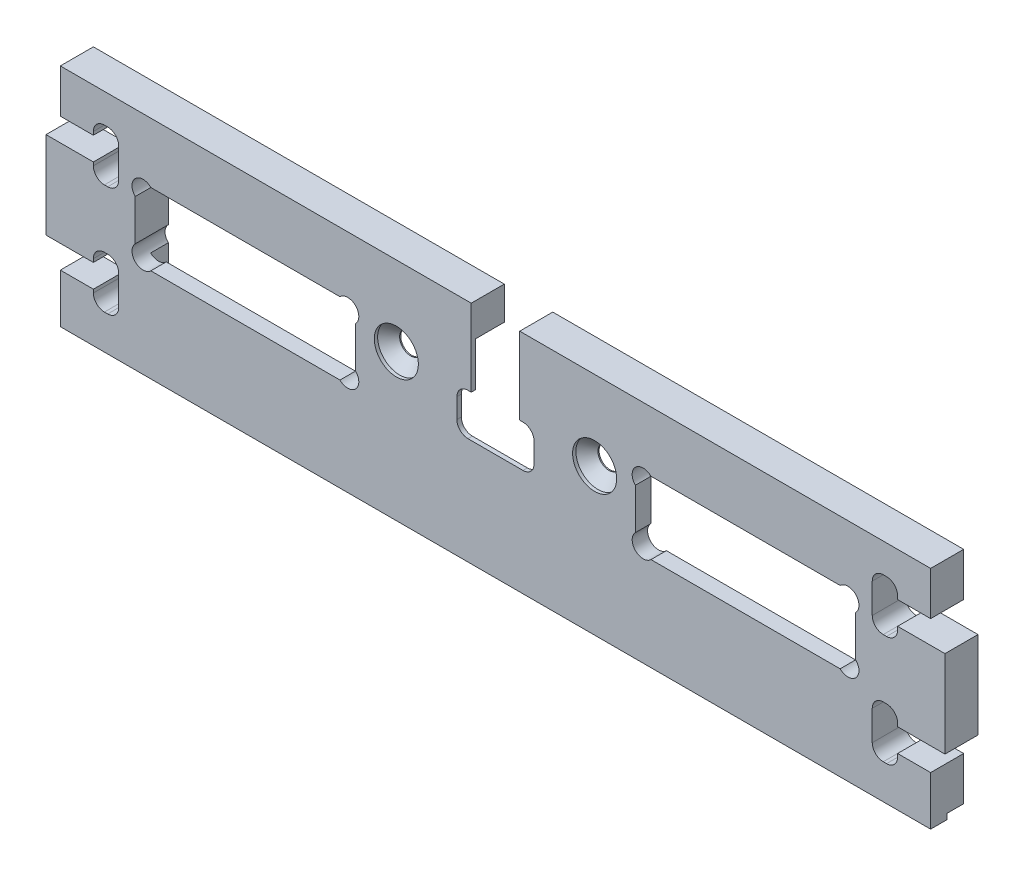
SolidWorks part; units mm, degrees
ref_plane "Front Plane" through (0, 0, 0) normal (0, 0, 1) x (1, 0, 0)
ref_plane "Top Plane" through (0, 0, 0) normal (0, 1, 0) x (1, 0, 0)
ref_plane "Right Plane" through (0, 0, 0) normal (1, 0, 0) x (0, 0, -1)
sketch "Sketch1" plane through (0, 0, 0) normal (0, 0, 1) x (1, 0, 0)
  line L0 (-39.5, 0) -> (39.5, 0) construction
  line L1 (-39.5, 10) -> (39.5, 10)
  line L2 (-39.5, 10) -> (-39.5, -10)
  line L3 (-39.5, -10) -> (39.5, -10)
  line L4 (39.5, 10) -> (39.5, -10)
  line L5 (-39.5, 10) -> (39.5, -10) construction
  line L6 (-39.5, -10) -> (39.5, 10) construction
  line L7 (0, 10) -> (0, -10) construction
  line L9 (-40.8, -3.95) -> (-39.5, -3.95)
  line L10 (-40.8, -3.95) -> (-40.8, 3.95)
  line L11 (-40.8, 3.95) -> (-39.5, 3.95)
  line L12 (-39.5, -3.95) -> (-39.5, 3.95)
  line L13 (-40.8, -3.95) -> (-39.5, 3.95) construction
  line L14 (-40.8, 3.95) -> (-39.5, -3.95) construction
  line L16 (40.8, 3.95) -> (39.5, 3.95)
  line L17 (40.8, -3.95) -> (40.8, 3.95)
  line L18 (40.8, -3.95) -> (39.5, -3.95)
  line L19 (-39.5, 5) -> (39.5, 5) construction
  line L20 (-35.35, 7.35) -> (-35.35, 2.65) construction
  line L21 (-36.5, 3.95) -> (-39.5, 3.95)
  line L22 (-36.5, 3.95) -> (-36.5, 6.05)
  line L23 (-36.5, 6.05) -> (-39.5, 6.05)
  line L24 (-39.5, 3.95) -> (-39.5, 6.05)
  line L25 (-36.5, 3.95) -> (-39.5, 6.05) construction
  line L26 (-36.5, 6.05) -> (-39.5, 3.95) construction
  line L27 (-34.2, 7.35) -> (-36.5, 7.35)
  line L28 (-34.2, 7.35) -> (-34.2, 2.65)
  line L29 (-34.2, 2.65) -> (-36.5, 2.65)
  line L30 (-36.5, 7.35) -> (-36.5, 2.65)
  line L31 (-34.2, 7.35) -> (-36.5, 2.65) construction
  line L32 (-34.2, 2.65) -> (-36.5, 7.35) construction
  line L33 (-34.2, -7.35) -> (-36.5, -7.35)
  line L34 (-34.2, -7.35) -> (-34.2, -2.65)
  line L35 (-34.2, -2.65) -> (-36.5, -2.65)
  line L36 (-36.5, -7.35) -> (-36.5, -2.65)
  line L37 (-36.5, -3.95) -> (-39.5, -3.95)
  line L38 (-36.5, -6.05) -> (-39.5, -6.05)
  line L39 (36.5, 3.95) -> (39.5, 3.95)
  line L40 (36.5, 6.05) -> (39.5, 6.05)
  line L41 (36.5, 7.35) -> (36.5, 2.65)
  line L42 (34.2, 7.35) -> (36.5, 7.35)
  line L43 (34.2, 7.35) -> (34.2, 2.65)
  line L44 (34.2, 2.65) -> (36.5, 2.65)
  line L45 (34.2, -2.65) -> (36.5, -2.65)
  line L46 (34.2, -7.35) -> (34.2, -2.65)
  line L47 (34.2, -7.35) -> (36.5, -7.35)
  line L48 (36.5, -7.35) -> (36.5, -2.65)
  line L49 (36.5, -6.05) -> (39.5, -6.05)
  line L50 (36.5, -3.95) -> (39.5, -3.95)
  point P0 (0, 0)
  point P10 (-40.15, 0)
  point P15 (-38, 5)
  point P35 (-35.35, 5)
  dimension "D1" = 79
  dimension "D2" = 20
  dimension "D4" = 1.3
  dimension "D7" = 5
  dimension "D8" = 2.1
  dimension "D9" = 3
  dimension "D10" = 2.3
  dimension "D11" = 4.7
extrude "Base shape" add sketch "Sketch1" along normal blind 3 contours L4 L1 L2 L3 | L9 L2 L11 L10 | L16 L4 L18 L17 region at (0, 0, 0) region at (-40.15, 0, 0) region at (40.15, 0, 0)
sketch "Sketch4" plane through (0, -10, 0) normal (0, -1, 0) x (1, 0, 0)
  line L0 (39.5, 3) -> (39.5, 0) construction
  line L1 (-39.5, 3) -> (39.5, 3)
  line L2 (-39.5, 3) -> (-39.5, 1.5)
  line L3 (-39.5, 1.5) -> (39.5, 1.5)
  line L4 (39.5, 3) -> (39.5, 1.5)
extrude "Floor lip" add sketch "Sketch4" along normal blind 0.5
sketch "Sketch6" plane through (0, 0, 0) normal (0, 0, -1) x (-1, 0, 0)
  line L0 (0, 0) -> (0, -10) construction
  line L1 (39.5, -10) -> (-39.5, -10) construction
  line L2 (-4, -10) -> (4, -10) construction
  line L3 (39.5, -10) -> (-39.5, -10) construction
  line L4 (-4, -9) -> (4, -9)
  line L5 (-4, -11) -> (4, -11)
  arc A0 (-4, -9) -> (-4, -11) centre (-4, -10) ccw
  arc A1 (4, -11) -> (4, -9) centre (4, -10) ccw
  point P9 (0, -10)
  dimension "D1" = 2
  dimension "D2" = 8
extrude "Nail cutout" cut sketch "Sketch6" against normal up to surface (1.5 mm away) up to face at (0, -10.25, 1.5)
sketch "Sketch3" plane through (-40.8, 0, 0) normal (-1, 0, 0) x (0, 0, 1)
  line L0 (0, 6.05) -> (3, 3.95) construction
  line L1 (0, 6.05) -> (3, 6.05)
  line L2 (0, 6.05) -> (0, 3.95)
  line L3 (0, 3.95) -> (3, 3.95)
  line L4 (3, 6.05) -> (3, 3.95)
  line L5 (0, -3.95) -> (3, -6.05) construction
  line L6 (0, -3.95) -> (3, -3.95)
  line L7 (0, -3.95) -> (0, -6.05)
  line L8 (0, -6.05) -> (3, -6.05)
  line L9 (3, -3.95) -> (3, -6.05)
  point P6 (1.5, 5)
  point P13 (1.5, -5)
ref_axis "Tap axis top" through (-53.7846, 5, 1.5) along (1, 0, 0)
ref_axis "Tap axis bottom" through (-54.2844, -5, 1.5) along (1, 0, 0)
fillet "Mill fillets" radius 1 16 edges at (36.5, -7.35, 1.5) (36.5, 2.65, 1.5) (34.2, 2.65, 1.5) (34.2, -7.35, 1.5) (36.5, -2.65, 1.5) (36.5, 7.35, 1.5) (34.2, -2.65, 1.5) (34.2, 7.35, 1.5) (-36.5, -2.65, 1.5) (-34.2, -2.65, 1.5) (-34.2, -7.35, 1.5) (-36.5, -7.35, 1.5) (-36.5, 2.65, 1.5) (-34.2, 2.65, 1.5) (-34.2, 7.35, 1.5) (-36.5, 7.35, 1.5)
sketch "Sketch8" [suppressed] plane through (0, 0, 3) normal (0, 0, 1) x (1, 0, 0)
  line L0 (-40.8, 0) -> (40.8, 0) construction
  line L1 (-40.8, -3.95) -> (-40.8, 3.95) construction
  line L2 (40.8, -3.95) -> (40.8, 3.95) construction
  line L4 (-24.5, 5.15) -> (24.5, 5.15)
  line L5 (-25.5, 4.15) -> (-25.5, -4.15)
  line L6 (-24.5, -5.15) -> (24.5, -5.15)
  line L7 (25.5, 4.15) -> (25.5, -4.15)
  line L8 (-25.5, 5.15) -> (25.5, -5.15) construction
  line L9 (-25.5, -5.15) -> (25.5, 5.15) construction
  arc A0 (24.5, -5.15) -> (25.5, -4.15) centre (24.5, -4.15) ccw
  arc A1 (24.5, 5.15) -> (25.5, 4.15) centre (24.5, 4.15) cw
  arc A2 (-25.5, -4.15) -> (-24.5, -5.15) centre (-24.5, -4.15) ccw
  arc A3 (-24.5, 5.15) -> (-25.5, 4.15) centre (-24.5, 4.15) ccw
  point P6 (0, 0)
  dimension "D3" = 1
  dimension "D1" = 51
  dimension "D2" = 10.3
extrude "Led strip pocket" [suppressed] cut sketch "Sketch8" against normal offset from surface (2.5 mm away) 0.5 up to face at (0, -0.6712, 0)
sketch "Sketch9" [suppressed] plane through (0, 0, 0.5) normal (0, 0, 1) x (1, 0, 0)
  line L0 (-19.5, 5.15) -> (-19.5, -5.15)
  line L1 (0, 5.15) -> (0, -5.15) construction
  line L2 (19.5, 5.15) -> (19.5, -5.15)
  line L3 (-25.5, -2.978) -> (25.5, -2.978) construction
  line L4 (25.5, -4.15) -> (25.5, 4.15)
  line L5 (24.5, 5.15) -> (-24.5, 5.15)
  line L6 (-25.5, 4.15) -> (-25.5, -4.15)
  line L7 (-24.5, -5.15) -> (24.5, -5.15)
  line L8 (25.5, -4.15) -> (25.5, 4.15)
  line L9 (24.5, 5.15) -> (-24.5, 5.15)
  line L10 (-25.5, 4.15) -> (-25.5, -4.15)
  line L11 (-24.5, -5.15) -> (24.5, -5.15)
  circle A0 centre (-12.7, -2.978) radius 1
  circle A1 centre (12.7, -2.978) radius 1
  arc A4 (24.5, -5.15) -> (25.5, -4.15) centre (24.5, -4.15) ccw
  arc A5 (25.5, 4.15) -> (24.5, 5.15) centre (24.5, 4.15) ccw
  arc A6 (-24.5, 5.15) -> (-25.5, 4.15) centre (-24.5, 4.15) ccw
  arc A7 (-25.5, -4.15) -> (-24.5, -5.15) centre (-24.5, -4.15) ccw
  arc A8 (24.5, -5.15) -> (25.5, -4.15) centre (24.5, -4.15) ccw
  arc A9 (25.5, 4.15) -> (24.5, 5.15) centre (24.5, 4.15) ccw
  arc A10 (-24.5, 5.15) -> (-25.5, 4.15) centre (-24.5, 4.15) ccw
  arc A11 (-25.5, -4.15) -> (-24.5, -5.15) centre (-24.5, -4.15) ccw
  arc M13 (24.5, -5.15) -> (25.5, -4.15) centre (24.5, -4.15) ccw
  line M14 (25.5, -4.15) -> (25.5, 4.15)
  arc M15 (25.5, 4.15) -> (24.5, 5.15) centre (24.5, 4.15) ccw
  line M16 (24.5, 5.15) -> (-24.5, 5.15)
  arc M17 (-24.5, 5.15) -> (-25.5, 4.15) centre (-24.5, 4.15) ccw
  line M18 (-25.5, 4.15) -> (-25.5, -4.15)
  arc M19 (-25.5, -4.15) -> (-24.5, -5.15) centre (-24.5, -4.15) ccw
  line M20 (-24.5, -5.15) -> (24.5, -5.15)
  dimension "D4" = 2
  dimension "D2" = 6
  dimension "D3" = 8.128
  dimension "D5" = 25.4
  dimension "D1" = 0
extrude "Led strip cuts" [suppressed] cut sketch "Sketch9" against normal up to next contours L0 M16 M17 M18 M19 M20 | L2 M16 M20 M13 M14 M15 | A0 | A1
fillet "Led strip cut fillets" [suppressed] radius 1
sketch "Sketch13" plane through (0, 0, 0) normal (0, 0, -1) x (-1, 0, 0)
  line L0 (0, 15.8648) -> (0, -21.9195) construction
  line L2 (-4.2, -6.3) -> (4.2, -6.3)
  line L3 (-5.2, -5.3) -> (-5.2, 6)
  line L4 (-4.2, 7) -> (4.2, 7)
  line L5 (5.2, -5.3) -> (5.2, 6)
  line L6 (-5.2, -6.3) -> (5.2, 7) construction
  line L7 (-5.2, 7) -> (5.2, -6.3) construction
  line L10 (39.5, 10) -> (-39.5, 10) construction
  arc A0 (-4.2, -6.3) -> (-5.2, -5.3) centre (-4.2, -5.3) cw
  arc A1 (4.2, -6.3) -> (5.2, -5.3) centre (4.2, -5.3) ccw
  arc A4 (5.2, 6) -> (4.2, 7) centre (4.2, 6) ccw
  arc A5 (-5.2, 6) -> (-4.2, 7) centre (-4.2, 6) cw
  point P1 (0, 0.35)
  dimension "D4" = 1
  dimension "D5" = 1
  dimension "D1" = 10.4
  dimension "D2" = 13.3
  dimension "D3" = 3
extrude "Bumper mount inner cut" cut sketch "Sketch13" against normal offset from surface (2.6 mm away) 0.4 up to face at (0, -0.0192, 3)
sketch "Sketch14" plane through (0, 0, 0) normal (0, 0, -1) x (-1, 0, 0)
  line L1 (0, 12.9528) -> (0, -14.0841) construction
  line L2 (4.2, 7) -> (-4.2, 7) construction
  line L3 (-4.2, -6.3) -> (4.2, -6.3) construction
  line L4 (-11.7, 7) -> (11.7, 7)
  line L5 (-12.7, 6) -> (-12.7, -5.3)
  line L6 (-11.7, -6.3) -> (11.7, -6.3)
  line L7 (12.7, 6) -> (12.7, -5.3)
  line L8 (-12.7, 7) -> (12.7, -6.3) construction
  line L9 (-12.7, -6.3) -> (12.7, 7) construction
  arc A1 (11.7, -6.3) -> (12.7, -5.3) centre (11.7, -5.3) ccw
  arc A2 (-12.7, -5.3) -> (-11.7, -6.3) centre (-11.7, -5.3) ccw
  arc A3 (11.7, 7) -> (12.7, 6) centre (11.7, 6) cw
  arc A4 (-12.7, 6) -> (-11.7, 7) centre (-11.7, 6) cw
  point P6 (0, 0.35)
  dimension "D2" = 1
  dimension "D3" = 1
  dimension "D1" = 25.4
extrude "Bumper mount outer cut" cut sketch "Sketch14" against normal blind 1.6
sketch "Sketch15" plane through (0, 0, 1.6) normal (0, 0, -1) x (-1, 0, 0)
  line L0 (-12.7, 2.8) -> (12.7, 2.8) construction
  line L3 (0, 16.4744) -> (0, -20.0474) construction
  line L7 (-12.7, 6) -> (-12.7, -5.3) construction
  line L8 (12.7, -5.3) -> (12.7, 6) construction
  line L11 (-4.2, 7) -> (-11.7, 7) construction
  circle A0 centre (-9, 2.8) radius 1
  circle A1 centre (9, 2.8) radius 1
  dimension "D1" = 18
  dimension "D2" = 2
  dimension "D3" = 4.2
extrude "Bumper mount screw holes" cut sketch "Sketch15" against normal up to next
sketch "Sketch16" plane through (0, 0, 2.6) normal (0, 0, -1) x (-1, 0, 0)
  line L0 (-5.2, 1.1) -> (5.2, 1.1) construction
  line L3 (0, 7) -> (0, -4.8) construction
  line L4 (-2.5, 3) -> (2.5, 3)
  line L5 (-3.5, 2) -> (-3.5, 0.2)
  line L6 (-2.5, -0.8) -> (2.5, -0.8)
  line L7 (3.5, 2) -> (3.5, 0.2)
  line L8 (-3.5, 3) -> (3.5, -0.8) construction
  line L9 (-3.5, -0.8) -> (3.5, 3) construction
  line L11 (-5.2, 6) -> (-5.2, -5.3) construction
  line L13 (4.2, 7) -> (-4.2, 7) construction
  arc A0 (2.5, -0.8) -> (3.5, 0.2) centre (2.5, 0.2) ccw
  arc A1 (-3.5, 0.2) -> (-2.5, -0.8) centre (-2.5, 0.2) ccw
  arc A2 (-2.5, 3) -> (-3.5, 2) centre (-2.5, 2) ccw
  arc A3 (2.5, 3) -> (3.5, 2) centre (2.5, 2) cw
  point P6 (0, 1.1)
  dimension "D3" = 1
  dimension "D1" = 7
  dimension "D2" = 3.8
  dimension "D4" = 11.8
extrude "Bumper body cut" cut sketch "Sketch16" against normal up to next
hole_wizard "Bumper screw countersunks" positions "Sketch17" profile "Sketch18" countersink size "M2" standard "ANSI Metric" end condition through all
sketch "Sketch17" plane through (0, 0, 3) normal (0, 0, 1) x (1, 0, 0)
  point P0 (9, 2.8)
  point P3 (-9, 2.8)
sketch "Sketch18" plane through (9, 2.8, 3) normal (1, 0, 0) x (0, -1, 0)
  line L0 (0, 0) -> (0, 3)
  line L1 (0, 3) -> (1, 3)
  line L2 (1, 3) -> (1, 1.3)
  line L3 (1, 1.3) -> (2, 0.3)
  line L4 (2, 0.3) -> (2, 0)
  line L6 (2, 0) -> (0, 0)
  line L7 (-1, 1.3) -> (-2, 0.3) construction
  line L11 (0, -6.35) -> (0, 107.95) construction
  dimension "Thru Hole Dia." = 2
  dimension "Thru Hole Depth" = 3
  dimension "C'Sink Dia." = 4
  dimension "C'Sink Angle" = 90
  dimension "Head Clearance" = 0.3
sketch "Sketch19" plane through (0, 0, 0) normal (0, 0, -1) x (-1, 0, 0)
  line L0 (0, 15.6498) -> (0, -12.9575) construction
  line L1 (39.5, 10) -> (-39.5, 10) construction
  line L2 (-2.2, 3) -> (2.2, 3)
  line L3 (-2.2, 3) -> (-2.2, 10)
  line L4 (-2.2, 10) -> (2.2, 10)
  line L5 (2.2, 3) -> (2.2, 10)
  line L6 (-2.2, 3) -> (2.2, 10) construction
  line L7 (-2.2, 10) -> (2.2, 3) construction
  line L8 (2.5, 3) -> (-2.5, 3) construction
  point P1 (0, 6.5)
  dimension "D1" = 4.4
extrude "Bumper insertion cut" cut sketch "Sketch19" against normal up to next
sketch "Sketch20" plane through (0, 0, 0) normal (0, 0, -1) x (-1, 0, 0)
  line L0 (-12.7, 6) -> (-12.7, -5.3) construction
  line L1 (-12.7, 4.55) -> (-32.7, 4.55)
  line L2 (-12.7, 4.55) -> (-12.7, -2)
  line L3 (-12.7, -2) -> (-32.7, -2)
  line L4 (-32.7, 4.55) -> (-32.7, -2)
  line L5 (-2.2, 10) -> (-39.5, 10) construction
  line L6 (-12.7, 4.55) -> (-19.25, -2) construction
  line L7 (-22.7, 4.55) -> (-22.7, -2) construction
  line L8 (-32.7, 1.275) -> (-12.7, 1.275) construction
  line L9 (0, 16.176) -> (0, -15.99) construction
  line L10 (12.7, 4.55) -> (12.7, -2)
  line L11 (12.7, -2) -> (32.7, -2)
  line L12 (32.7, 4.55) -> (32.7, -2)
  line L13 (12.7, 4.55) -> (32.7, 4.55)
  circle A0 centre (-13.4071, 3.8429) radius 1
  circle A1 centre (-31.9929, 3.8429) radius 1
  circle A2 centre (-13.4071, -1.2929) radius 1
  circle A3 centre (-31.9929, -1.2929) radius 1
  circle A4 centre (13.4071, 3.8429) radius 1
  circle A5 centre (13.4071, -1.2929) radius 1
  circle A6 centre (31.9929, -1.2929) radius 1
  circle A7 centre (31.9929, 3.8429) radius 1
  dimension "D5" = 2
  dimension "D1" = 20
  dimension "D2" = 5.45
  dimension "D3" = 6.55
  dimension "D4" = 45
extrude "Bumper switches cut" cut sketch "Sketch20" against normal up to next contours L1 L4 L3 L2 | A1 | A3 | A0 | A2 | L13 L12 L11 L10 | A4 | A5 | A6 | A7
sketch "Sketch21" plane through (0, 0, 0) normal (0, 0, -1) x (-1, 0, 0)
  line L0 (-14.1142, -2) -> (-31.2858, -2) construction
  line L1 (-32.7, -2) -> (-12.7, -2)
  line L2 (-32.7, -2) -> (-32.7, -6.3)
  line L3 (-32.7, -6.3) -> (-12.7, -6.3)
  line L4 (-12.7, -2) -> (-12.7, -6.3)
  line L5 (-12.7, -2) -> (-12.7, -5.3) construction
  line L6 (-11.7, -6.3) -> (-4.2, -6.3) construction
  line L7 (-32.7, 3.1358) -> (-32.7, -0.5858) construction
  line L8 (-12.7, -6.3) -> (-11.7, -6.3)
  line L9 (-32.7, -6.3) -> (-28.4, -2) construction
  line L10 (0, 14.2019) -> (0, -15.3745) construction
  line L11 (12.7, -6.3) -> (11.7, -6.3)
  line L12 (12.7, -2) -> (12.7, -6.3)
  line L13 (32.7, -2) -> (12.7, -2)
  line L14 (32.7, -2) -> (32.7, -6.3)
  line L15 (32.7, -6.3) -> (12.7, -6.3)
  arc A0 (-12.7, -5.3) -> (-11.7, -6.3) centre (-11.7, -5.3) ccw construction
  arc A1 (-12.7, -5.3) -> (-11.7, -6.3) centre (-11.7, -5.3) ccw
  circle A2 centre (-31.9929, -5.5929) radius 1
  arc A3 (-32.7, -0.5858) -> (-31.2858, -2) centre (-31.9929, -1.2929) ccw construction
  circle A4 centre (31.9929, -5.5929) radius 1
  arc A5 (12.7, -5.3) -> (11.7, -6.3) centre (11.7, -5.3) cw
  dimension "D1" = 45
extrude "Bumper switch mounts cut" cut sketch "Sketch21" against normal up to surface (1.6 mm away) contours A1 L4 L8 | L12 A5 L11 | L4 L1 L2 L3 | A2 | L12 L13 L14 L15 | A4 region at (12.4766, -6.0766, 0) region at (-12.4766, -6.0766, 0) up to face at (-8, 2.8, 1.6)
sketch "Outer coordinate system sketch" plane through (0, 0, 3) normal (0, 0, 1) x (1, 0, 0)
  line L0 (-35.35, 7.35) -> (-35.35, 2.65) construction
  line L1 (-35.2, 7.35) -> (-35.5, 7.35) construction
  line L2 (-40.8, 3.95) -> (-40.8, 10) construction
  line L3 (-40.8, 10) -> (-39.5, 10) construction
  line L4 (-35.2, 2.65) -> (-35.5, 2.65) construction
  line L5 (0, 15.526) -> (0, -17.3739) construction
  line L6 (-51.2617, 0) -> (56.0692, 0) construction
  circle A0 centre (-35.35, 6.35) radius 1
  point P16 (-35.35, 6.35)
  point P22 (35.35, 6.35)
  point P24 (-35.35, -6.35)
  point P25 (35.35, -6.35)
  dimension "D1" = 2
sketch "Inner coordinate system sketch" plane through (0, 0, 0) normal (0, 0, 1) x (1, 0, 0)
  line L0 (-40.8, -3.95) -> (-40.8, -10) construction
  line L1 (-40.8, -10) -> (-39.5, -10) construction
  line L3 (0, 19.9465) -> (0, -19.5427) construction
  line L4 (53.9633, 0) -> (-51.6097, 0) construction
sketch "Deep inner pocket mill sketch" plane through (0, 0, 2.6) normal (0, 0, -1) x (-1, 0, 0)
  line L0 (-4.2, 7) -> (4.2, 7)
  line L12 (4.2, 7) -> (2.2, 7)
  line L13 (2.2, 7) -> (2.2, 3)
  line L14 (2.2, 3) -> (2.5, 3)
  line L15 (3.5, 2) -> (3.5, 0.2)
  line L16 (2.5, -0.8) -> (-2.5, -0.8)
  line L17 (-3.5, 0.2) -> (-3.5, 2)
  line L18 (-2.5, 3) -> (-2.2, 3)
  line L19 (-2.2, 3) -> (-2.2, 7)
  line L20 (-2.2, 7) -> (-4.2, 7)
  line L21 (-5.2, 6) -> (-5.2, -5.3)
  line L22 (-4.2, -6.3) -> (4.2, -6.3)
  line L23 (5.2, -5.3) -> (5.2, 6)
  line L33 (-5.2, 6) -> (-5.2, -5.3)
  line L34 (-4.2, -6.3) -> (4.2, -6.3)
  line L35 (5.2, -5.3) -> (5.2, 6)
  arc A8 (3.5, 2) -> (2.5, 3) centre (2.5, 2) ccw
  arc A9 (2.5, -0.8) -> (3.5, 0.2) centre (2.5, 0.2) ccw
  arc A10 (-3.5, 0.2) -> (-2.5, -0.8) centre (-2.5, 0.2) ccw
  arc A11 (-2.5, 3) -> (-3.5, 2) centre (-2.5, 2) ccw
  arc A12 (-4.2, 7) -> (-5.2, 6) centre (-4.2, 6) ccw
  arc A13 (-5.2, -5.3) -> (-4.2, -6.3) centre (-4.2, -5.3) ccw
  arc A14 (4.2, -6.3) -> (5.2, -5.3) centre (4.2, -5.3) ccw
  arc A15 (5.2, 6) -> (4.2, 7) centre (4.2, 6) ccw
  arc A20 (-4.2, 7) -> (-5.2, 6) centre (-4.2, 6) ccw
  arc A21 (-5.2, -5.3) -> (-4.2, -6.3) centre (-4.2, -5.3) ccw
  arc A22 (4.2, -6.3) -> (5.2, -5.3) centre (4.2, -5.3) ccw
  arc A23 (5.2, 6) -> (4.2, 7) centre (4.2, 6) ccw
  dimension "D1" = 0
sketch "Shallow inner pocket mill sketch" plane through (0, 0, 1.6) normal (0, 0, -1) x (-1, 0, 0)
  line L2 (12.7, 4.55) -> (12.7, 6) construction
  line L7 (-12.7, 6) -> (-12.7, 4.55) construction
  line L16 (12.7, 4.55) -> (12.7, 6)
  line L21 (-12.7, 6) -> (-12.7, 4.55)
  line L42 (-32.7, -1) -> (-13.7, -1)
  line L43 (-12.7, 3.1358) -> (-12.7, -0.5858) construction
  line L47 (0, 16.1275) -> (0, -14.7685) construction
  line L53 (-31.2858, -6.3) -> (31.2858, -6.3)
  line L54 (-11.7, 7) -> (11.7, 7)
  line L55 (-12.7, 4.55) -> (-13.7, 4.55)
  line L56 (-13.7, 4.55) -> (-13.7, -1)
  line L58 (-22.7, -2) -> (-22.7, -1) construction
  line L59 (-31.2858, -2) -> (-14.1142, -2) construction
  line L60 (-12.7, 1.275) -> (-13.7, 1.275) construction
  line L61 (-32.7, -1) -> (-32.7, -4.8858)
  line L62 (12.7, 4.55) -> (13.7, 4.55)
  line L63 (13.7, 4.55) -> (13.7, -1)
  line L64 (32.7, -1) -> (13.7, -1)
  line L65 (32.7, -1) -> (32.7, -4.8858)
  arc A2 (12.7, 6) -> (11.7, 7) centre (11.7, 6) ccw construction
  arc A5 (31.2858, -6.3) -> (32.7, -4.8858) centre (31.9929, -5.5929) ccw construction
  arc A10 (-32.7, -4.8858) -> (-31.2858, -6.3) centre (-31.9929, -5.5929) ccw construction
  arc A13 (-11.7, 7) -> (-12.7, 6) centre (-11.7, 6) ccw construction
  arc A16 (12.7, 6) -> (11.7, 7) centre (11.7, 6) ccw
  arc A19 (31.2858, -6.3) -> (32.7, -4.8858) centre (31.9929, -5.5929) ccw
  arc A24 (-32.7, -4.8858) -> (-31.2858, -6.3) centre (-31.9929, -5.5929) ccw
  arc A27 (-11.7, 7) -> (-12.7, 6) centre (-11.7, 6) ccw
  dimension "D1" = 1
